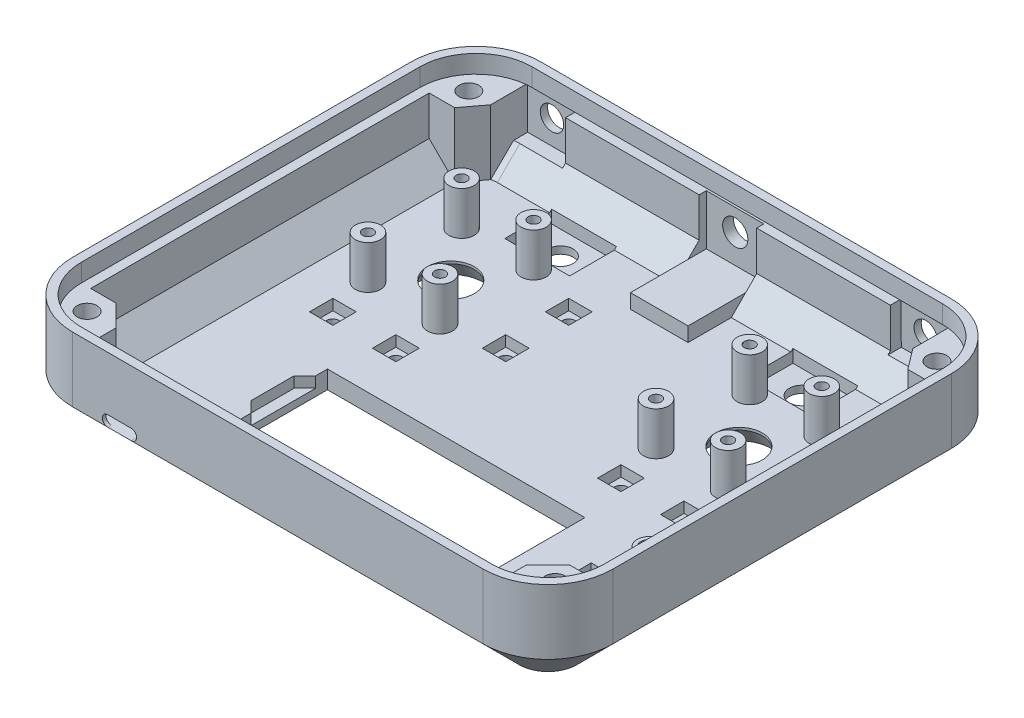
SolidWorks part; units mm, degrees
ref_plane "前视基准面" through (0, 0, 0) normal (0, 0, 1) x (1, 0, 0)
ref_plane "上视基准面" through (0, 0, 0) normal (0, 1, 0) x (1, 0, 0)
ref_plane "右视基准面" through (0, 0, 0) normal (1, 0, 0) x (0, 0, -1)
other "Configuration Table"
sketch "草图1" plane through (0, 0, 0) normal (0, 1, 0) x (1, 0, 0)
  line L1 (-57, -65) -> (57, -65)
  line L2 (-75, -47) -> (-75, 47)
  line L3 (-57, 65) -> (57, 65)
  line L4 (75, -47) -> (75, 47)
  line L5 (-75, -65) -> (75, 65) construction
  line L6 (-75, 65) -> (75, -65) construction
  arc A0 (57, -65) -> (75, -47) centre (57, -47) ccw
  arc A1 (-57, -65) -> (-75, -47) centre (-57, -47) cw
  arc A2 (-75, 47) -> (-57, 65) centre (-57, 47) cw
  arc A3 (57, 65) -> (75, 47) centre (57, 47) cw
  point P0 (0, 0)
  dimension "D3" = 18
  dimension "D1" = 150
  dimension "D2" = 130
extrude "凸台-拉伸1" add sketch "草图1" along normal blind 23
chamfer "倒角1" distance 10 angle 45 8 edges at (75, 0, 0) (69.7279, 0, -59.7279) (0, 0, -65) (-69.7279, 0, -59.7279) (-75, 0, 0) (-69.7279, 0, 59.7279) (0, 0, 65) (69.7279, 0, 59.7279)
shell "抽壳3" thickness 5 removed face at (0, 23, 0)
sketch "草图2" plane through (0, 0, -65) normal (0, 0, -1) x (-1, 0, 0)
  line L0 (0, 0) -> (0, 23) construction
  line L1 (-57, 23) -> (57, 23) construction
  circle A0 centre (0, 17) radius 3.5
  circle A1 centre (-51.8897, 18) radius 3.25
  circle A2 centre (51.8897, 18) radius 3.25
  dimension "D1" = 7
  dimension "D2" = 6.5
  dimension "D3" = 5
  dimension "D4" = 6
extrude "切除-拉伸1" cut sketch "草图2" against normal blind 27
sketch "草图3" plane through (0, 0, 0) normal (0, -1, 0) x (1, 0, 0)
  line L0 (0, 0) -> (0, -65) construction
  line L1 (57, -65) -> (-57, -65) construction
  line L2 (-57, -55) -> (57, -55) construction
  line L3 (40, -23) -> (40, 55) construction
  line L4 (57, 55) -> (-57, 55) construction
  line L5 (65, -47) -> (65, 47) construction
  line L6 (60, 25.5) -> (47.5, 25.5)
  line L7 (60, 25.5) -> (60, 45)
  line L8 (60, 45) -> (47.5, 45)
  line L9 (47.5, 25.5) -> (47.5, 45)
  line L11 (35.75, 40) -> (-35.75, 40)
  line L12 (35.75, 40) -> (35.75, 15.5)
  line L13 (35.75, 15.5) -> (-35.75, 15.5)
  line L14 (-35.75, 40) -> (-35.75, 15.5)
  line L15 (35.75, 40) -> (-35.75, 15.5) construction
  line L16 (35.75, 15.5) -> (-35.75, 40) construction
  circle A0 centre (33.5, -47) radius 3.5
  circle A1 centre (-33.5, -47) radius 3.5
  circle A2 centre (40, -23) radius 6
  circle A3 centre (-40, -23) radius 6
  circle A4 centre (48.75, 1) radius 1.8
  circle A5 centre (31.25, 1) radius 1.8
  circle A6 centre (-31.25, 1) radius 1.8
  circle A7 centre (-48.75, 1) radius 1.8
  circle A8 centre (-16, -31.75) radius 1.8
  circle A9 centre (-16, -14.25) radius 1.8
  arc A14 (-30.3728, -45.4282) -> (-30.3728, -48.5718) centre (-31.25, -47) cw [skipped]
  circle A15 centre (-48.75, -47) radius 1.8 [skipped]
  circle A16 centre (-64, -31.75) radius 1.8 [skipped]
  circle A17 centre (-64, -14.25) radius 1.8 [skipped]
  circle A18 centre (53.75, 15.5) radius 2.5
  point P38 (0, 27.75)
  point P41 (-40, -23)
  dimension "D1" = 7
  dimension "D2" = 67
  dimension "D3" = 8
  dimension "D5" = 80
  dimension "D6" = 12
  dimension "D7" = 3.6
  dimension "D8" = 17.5
  dimension "D9" = 24
  dimension "D15" = 5
  dimension "D4" = 32
  dimension "D11" = 19.5
  dimension "D12" = 12.5
  dimension "D13" = 5
  dimension "D14" = 10
  dimension "D16" = 10
  dimension "D17" = 71.5
  dimension "D18" = 24.5
  dimension "D19" = 15
  dimension "D10" = 4
extrude "切除-拉伸2" cut sketch "草图3" against normal blind 27
sketch "草图4" plane through (0, 5, 0) normal (0, 1, 0) x (1, 0, 0)
  circle A0 centre (53.75, -15.5) radius 3.5
  circle A1 centre (53.75, -15.5) radius 2.5
  dimension "D1" = 5
  dimension "D2" = 7
extrude "凸台-拉伸2" add sketch "草图4" along normal blind 2
sketch "草图6" plane through (0, 5, 0) normal (0, 1, 0) x (1, 0, 0)
  line L0 (0, 0) -> (0, 65) construction
  line L1 (24.5, 40.5) -> (42.5, 40.5)
  line L2 (24.5, 40.5) -> (24.5, 53.5)
  line L3 (24.5, 53.5) -> (42.5, 53.5)
  line L4 (42.5, 40.5) -> (42.5, 53.5)
  line L5 (24.5, 40.5) -> (42.5, 53.5) construction
  line L6 (24.5, 53.5) -> (42.5, 40.5) construction
  line L7 (57, 65) -> (-57, 65) construction
  line L8 (-24.5, 53.5) -> (-42.5, 53.5)
  line L9 (-42.5, 40.5) -> (-42.5, 53.5)
  line L10 (-24.5, 40.5) -> (-42.5, 40.5)
  line L11 (-24.5, 40.5) -> (-24.5, 53.5)
  point P0 (33.5, 47)
  dimension "D1" = 13
  dimension "D2" = 18
extrude "切除-拉伸3" cut sketch "草图6" against normal mid plane 6
sketch "草图7" plane through (0, 23, 0) normal (0, 1, 0) x (1, 0, 0)
  line L6 (57, 65) -> (-57, 65) construction
  line L7 (-8.0392, 52.4354) -> (7.9608, 52.4354)
  line L8 (-8.0392, 52.4354) -> (-8.0392, 62)
  line L9 (-8.0392, 62) -> (7.9608, 62)
  line L10 (7.9608, 52.4354) -> (7.9608, 62)
  line L11 (-8.0392, 52.4354) -> (7.9608, 62) construction
  line L12 (-8.0392, 62) -> (7.9608, 52.4354) construction
  point P0 (-0.0392, 57.2177)
  dimension "D1" = 16
  dimension "D2" = 3
extrude "切除-拉伸8" cut sketch "草图7" against normal blind 14
sketch "草图8" plane through (0, 0, -60) normal (0, 0, 1) x (1, 0, 0)
  line L0 (0, 0) -> (-0.0392, 23) construction
  line L1 (-58.6397, 11.25) -> (-45.1397, 11.25)
  line L2 (-58.6397, 11.25) -> (-58.6397, 24.75)
  line L3 (-58.6397, 24.75) -> (-45.1397, 24.75)
  line L4 (-45.1397, 11.25) -> (-45.1397, 24.75)
  line L5 (-58.6397, 11.25) -> (-45.1397, 24.75) construction
  line L6 (-58.6397, 24.75) -> (-45.1397, 11.25) construction
  line L7 (-57, 0) -> (57, 0) construction
  line L8 (7.9608, 23) -> (-8.0392, 23) construction
  line L9 (58.5549, 24.95) -> (45.0549, 24.9039)
  line L10 (45.101, 11.404) -> (45.0549, 24.9039)
  line L11 (58.6009, 11.4501) -> (45.101, 11.404)
  line L12 (58.6009, 11.4501) -> (58.5549, 24.95)
  point P0 (-51.8897, 18)
  dimension "D1" = 13.5
  dimension "D2" = 13.5
extrude "切除-拉伸9" cut sketch "草图8" along normal blind 13 from offset 3 offset against normal yes
sketch "草图9" plane through (0, 5, 0) normal (0, 1, 0) x (1, 0, 0)
  line L1 (-52, -4.25) -> (-45.5, -4.25)
  line L2 (-52, -4.25) -> (-52, 2.25)
  line L3 (-52, 2.25) -> (-45.5, 2.25)
  line L4 (-45.5, -4.25) -> (-45.5, 2.25)
  line L5 (-52, -4.25) -> (-45.5, 2.25) construction
  line L6 (-52, 2.25) -> (-45.5, -4.25) construction
  line L7 (-34.5, -4.25) -> (-28, -4.25)
  line L8 (-34.5, -4.25) -> (-34.5, 2.25)
  line L9 (-34.5, 2.25) -> (-28, 2.25)
  line L10 (-28, -4.25) -> (-28, 2.25)
  line L11 (-34.5, -4.25) -> (-28, 2.25) construction
  line L12 (-34.5, 2.25) -> (-28, -4.25) construction
  line L13 (0, 0) -> (0, 52.9289) construction
  line L14 (-24.5, 52.9289) -> (24.5, 52.9289) construction
  line L15 (34.5, 2.25) -> (28, -4.25) construction
  line L16 (34.5, -4.25) -> (28, 2.25) construction
  line L17 (52, 2.25) -> (45.5, -4.25) construction
  line L18 (52, -4.25) -> (45.5, 2.25) construction
  line L19 (28, -4.25) -> (28, 2.25)
  line L20 (34.5, 2.25) -> (28, 2.25)
  line L21 (34.5, -4.25) -> (34.5, 2.25)
  line L22 (34.5, -4.25) -> (28, -4.25)
  line L23 (45.5, -4.25) -> (45.5, 2.25)
  line L24 (52, 2.25) -> (45.5, 2.25)
  line L25 (52, -4.25) -> (52, 2.25)
  line L26 (52, -4.25) -> (45.5, -4.25)
  line L43 (-12.75, 11) -> (-19.25, 11)
  line L44 (-12.75, 11) -> (-12.75, 17.5)
  line L45 (-12.75, 17.5) -> (-19.25, 17.5)
  line L46 (-19.25, 11) -> (-19.25, 17.5)
  line L47 (-12.75, 28.5) -> (-19.25, 28.5)
  line L48 (-12.75, 28.5) -> (-12.75, 35)
  line L49 (-12.75, 35) -> (-19.25, 35)
  line L50 (-19.25, 28.5) -> (-19.25, 35)
  line L51 (-28, 50.25) -> (-28, 43.75) [skipped]
  line L52 (-34.5, 50.25) -> (-34.5, 43.75) [skipped]
  line L53 (-45.5, 50.25) -> (-45.5, 43.75) [skipped]
  line L54 (-52, 50.25) -> (-52, 43.75) [skipped]
  line L55 (-45.5, 43.75) -> (-52, 43.75) [skipped]
  line L56 (-45.5, 50.25) -> (-52, 50.25) [skipped]
  line L57 (-28, 50.25) -> (-34.5, 50.25) [skipped]
  line L58 (-28, 43.75) -> (-34.5, 43.75) [skipped]
  line L59 (-67.25, 35) -> (-60.75, 35) [skipped]
  line L60 (-67.25, 28.5) -> (-60.75, 28.5) [skipped]
  line L61 (-60.75, 35) -> (-60.75, 28.5) [skipped]
  line L62 (-67.25, 35) -> (-67.25, 28.5) [skipped]
  line L63 (-67.25, 17.5) -> (-60.75, 17.5) [skipped]
  line L64 (-60.75, 17.5) -> (-60.75, 11) [skipped]
  line L65 (-67.25, 17.5) -> (-67.25, 11) [skipped]
  line L66 (-67.25, 11) -> (-60.75, 11) [skipped]
  point P0 (-48.75, -1)
  point P6 (-31.25, -1)
  point P12 (-40, 23)
  point P27 (31.25, -1)
  point P28 (48.75, -1)
  point P56 (-40, 23)
  dimension "D1" = 6.5
  dimension "D2" = 6.5
  dimension "D3" = 6.5
  dimension "D4" = 6.5
  dimension "D5" = 4
extrude "切除-拉伸10" cut sketch "草图9" against normal mid plane 6
sketch "草图10" plane through (0, 5, 0) normal (0, 1, 0) x (1, 0, 0)
  line L0 (-35.75, -15.5) -> (-35.75, -40) construction
  line L1 (-32.75, -33.75) -> (-38.75, -33.75)
  line L2 (-32.75, -33.75) -> (-32.75, -21.75)
  line L3 (-32.75, -21.75) -> (-38.75, -21.75)
  line L4 (-38.75, -33.75) -> (-38.75, -21.75)
  line L5 (-32.75, -33.75) -> (-38.75, -21.75) construction
  line L6 (-32.75, -21.75) -> (-38.75, -33.75) construction
  point P0 (-35.75, -27.75)
  dimension "D1" = 12
  dimension "D2" = 6
extrude "切除-拉伸11" cut sketch "草图10" against normal mid plane 6
chamfer "倒角2" distance 3 angle 45 2 edges at (-35.75, 3.5, 33.75) (-35.75, 3.5, 21.75)
sketch "草图11" plane through (0, 0, 0) normal (0, -1, 0) x (1, 0, 0)
  circle A0 centre (40, -23) radius 6.5
  circle A1 centre (-40, -23) radius 6.5
  dimension "D1" = 13
  dimension "D2" = 13
extrude "切除-拉伸12" cut sketch "草图11" against normal blind 6
chamfer "倒角3" distance 2.5 angle 60 2 edges at (40, 0, -29.5) (-40, 0, -29.5) first distance on face at (40, 0, -29.5)
sketch "草图12" plane through (0, 5, 0) normal (0, 1, 0) x (1, 0, 0)
  line L0 (0, 0) -> (0, 52.9289) construction
  line L1 (-24.5, 52.9289) -> (24.5, 52.9289) construction
  circle A0 centre (29, 37) radius 1.5
  circle A1 centre (29, 11) radius 1.5
  circle A2 centre (49, 11) radius 1.5
  circle A3 centre (49, 37) radius 1.5
  circle A4 centre (29, 37) radius 3.5
  circle A5 centre (49, 37) radius 3.5
  circle A6 centre (49, 11) radius 3.5
  circle A7 centre (29, 11) radius 3.5
  circle A16 centre (-31, 37) radius 1.5
  circle A17 centre (-51, 37) radius 1.5
  circle A18 centre (-51, 11) radius 1.5
  circle A19 centre (-31, 11) radius 1.5
  circle A20 centre (-31, 37) radius 3.5
  circle A21 centre (-51, 37) radius 3.5
  circle A22 centre (-51, 11) radius 3.5
  circle A23 centre (-31, 11) radius 3.5
  point P8 (40, 23)
  point P35 (-40, 23)
  dimension "D1" = 3
  dimension "D2" = 3
  dimension "D3" = 3
  dimension "D4" = 3
  dimension "D5" = 20
  dimension "D6" = 26
  dimension "D7" = 9
  dimension "D8" = 12
  dimension "D9" = 7
  dimension "D10" = 7
  dimension "D11" = 7
  dimension "D12" = 3
  dimension "D13" = 3
  dimension "D14" = 3
  dimension "D15" = 3
  dimension "D16" = 20
  dimension "D17" = 26
  dimension "D20" = 14
  dimension "D19" = 9
  dimension "D18" = 2
extrude "凸台-拉伸3" add sketch "草图12" along normal blind 12
sketch "草图13" plane through (0, 0, 60) normal (0, 0, -1) x (-1, 0, 0)
  line L0 (57, 23) -> (-57, 23) construction
  line L1 (34, 10) -> (54, 10)
  line L2 (34, 10) -> (34, 20)
  line L3 (34, 20) -> (54, 20)
  line L4 (54, 10) -> (54, 20)
  line L5 (34, 10) -> (54, 20) construction
  line L6 (34, 20) -> (54, 10) construction
  line L7 (57, 23) -> (57, 12.0711) construction
  point P0 (44, 15)
  dimension "D1" = 10
  dimension "D2" = 20
  dimension "D3" = 3
  dimension "D4" = 3
extrude "切除-拉伸13" cut sketch "草图13" against normal blind 4 contours L4 L3 L2 L1
sketch "草图14" plane through (0, 0, 64) normal (0, 0, -1) x (-1, 0, 0)
  line L0 (40.75, 11.5) -> (47.25, 11.5) construction
  line L1 (40.75, 13) -> (47.25, 13)
  line L2 (40.75, 10) -> (47.25, 10)
  line L3 (34, 10) -> (54, 10) construction
  arc A0 (40.75, 13) -> (40.75, 10) centre (40.75, 11.5) ccw
  arc A1 (47.25, 10) -> (47.25, 13) centre (47.25, 11.5) ccw
  point P2 (44, 11.5)
  point P7 (39.25, 11.5)
  point P8 (48.75, 11.5)
  point P9 (44, 10)
  dimension "D1" = 9.5
  dimension "D2" = 3
extrude "切除-拉伸14" cut sketch "草图14" against normal blind 4
sketch "草图15" plane through (0, 23, 0) normal (0, 1, 0) x (1, 0, 0)
  line L20 (72.6, -47) -> (72.6, 47)
  line L21 (-57, -62.6) -> (57, -62.6)
  line L22 (-72.6, 47) -> (-72.6, -47)
  line L23 (57, 62.6) -> (-57, 62.6)
  line L24 (72.6, -47) -> (72.6, 47)
  line L25 (-57, -62.6) -> (57, -62.6)
  line L26 (-72.6, 47) -> (-72.6, -47)
  line L27 (57, 62.6) -> (-57, 62.6)
  line L44 (75, -47) -> (75, 47)
  line L45 (-57, -65) -> (57, -65)
  line L46 (-75, 47) -> (-75, -47)
  line L47 (57, 65) -> (-57, 65)
  line L48 (75, -47) -> (75, 47)
  line L49 (-57, -65) -> (57, -65)
  line L50 (-75, 47) -> (-75, -47)
  line L51 (57, 65) -> (-57, 65)
  arc A24 (57, -62.6) -> (72.6, -47) centre (57, -47) ccw
  arc A25 (-72.6, -47) -> (-57, -62.6) centre (-57, -47) ccw
  arc A26 (-57, 62.6) -> (-72.6, 47) centre (-57, 47) ccw
  arc A27 (72.6, 47) -> (57, 62.6) centre (57, 47) ccw
  arc A28 (57, -62.6) -> (72.6, -47) centre (57, -47) ccw
  arc A29 (-72.6, -47) -> (-57, -62.6) centre (-57, -47) ccw
  arc A30 (-57, 62.6) -> (-72.6, 47) centre (-57, 47) ccw
  arc A31 (72.6, 47) -> (57, 62.6) centre (57, 47) ccw
  arc A52 (57, -65) -> (75, -47) centre (57, -47) ccw
  arc A53 (-75, -47) -> (-57, -65) centre (-57, -47) ccw
  arc A54 (-57, 65) -> (-75, 47) centre (-57, 47) ccw
  arc A55 (75, 47) -> (57, 65) centre (57, 47) ccw
  arc A56 (57, -65) -> (75, -47) centre (57, -47) ccw
  arc A57 (-75, -47) -> (-57, -65) centre (-57, -47) ccw
  arc A58 (-57, 65) -> (-75, 47) centre (-57, 47) ccw
  arc A59 (75, 47) -> (57, 65) centre (57, 47) ccw
  dimension "D4" = 18
  dimension "D3" = 150
  dimension "D5" = 130
  dimension "D6" = 145.2
  dimension "D1" = 2.4
  dimension "D2" = 0
extrude "凸台-拉伸4" add sketch "草图15" along normal blind 5
sketch "草图26" plane through (0, 0, 0) normal (0, -1, 0) x (1, 0, 0)
  text T0 "<b>              PTSFDTZ</b>" font "@Adobe Gothic Std B" height 10
extrude "切除-拉伸16" cut sketch "草图26" against normal blind 1
sketch "草图27" plane through (0, 23, 0) normal (0, 1, 0) x (1, 0, 0)
  line L0 (70, -47) -> (62.9289, -47)
  line L1 (58.5988, 52.7076) -> (62.9289, 47)
  line L2 (57, -52.9289) -> (57, -60)
  line L3 (58.5988, 59.9013) -> (58.5988, 52.7076)
  line L4 (70, 47) -> (62.9289, 47)
  line L5 (-58.6397, 59.8962) -> (-58.6397, 52.6977)
  line L6 (-70, 47) -> (-62.9289, 47)
  line L7 (-70, -47) -> (-62.9289, -47)
  line L8 (-62.9289, -47) -> (-57, -52.9289)
  line L9 (-57, -52.9289) -> (-57, -60)
  line L10 (62.9289, -47) -> (57, -52.9289)
  line L11 (-58.6397, 52.6977) -> (-62.9289, 47)
  arc A0 (-70, -47) -> (-57, -60) centre (-57, -47) ccw
  arc A2 (-58.6397, 59.8962) -> (-70, 47) centre (-57, 47) ccw
  arc A4 (70, 47) -> (58.5988, 59.9013) centre (57, 47) ccw
  arc A6 (57, -60) -> (70, -47) centre (57, -47) ccw
extrude "凸台-拉伸5" add sketch "草图27" against normal up to next
sketch "草图28" plane through (0, 23, 0) normal (0, 1, 0) x (1, 0, 0)
  line L0 (57, 65) -> (-57, 65) construction
  line L1 (75, -47) -> (75, 47) construction
  line L2 (0, 0) -> (0, 65) construction
  line L3 (0, 0) -> (75, 0) construction
  line L4 (-57, -65) -> (57, -65) construction
  circle A0 centre (65, 53) radius 2.75
  circle A1 centre (-65, 53) radius 2.75
  circle A2 centre (-65, -53) radius 2.75
  circle A3 centre (65, -53) radius 2.75
  dimension "D1" = 5.5
  dimension "D3" = 10
  dimension "D2" = 12
  dimension "D4" = 12
extrude "切除-拉伸17" cut sketch "草图28" against normal blind 4
sketch "草图29" plane through (0, 5, 0) normal (0, 1, 0) x (1, 0, 0)
  line L1 (-8.0392, 56.9289) -> (7.9608, 56.9289)
  line L2 (-8.0392, 56.9289) -> (-8.0392, 40.9289)
  line L3 (-8.0392, 40.9289) -> (7.9608, 40.9289)
  line L4 (7.9608, 56.9289) -> (7.9608, 40.9289)
  dimension "D1" = 16
  dimension "D2" = 16
extrude "凸台-拉伸6" add sketch "草图29" along normal blind 4
equation "\"4‘\"=3"
equation "\"198、\"=17"
